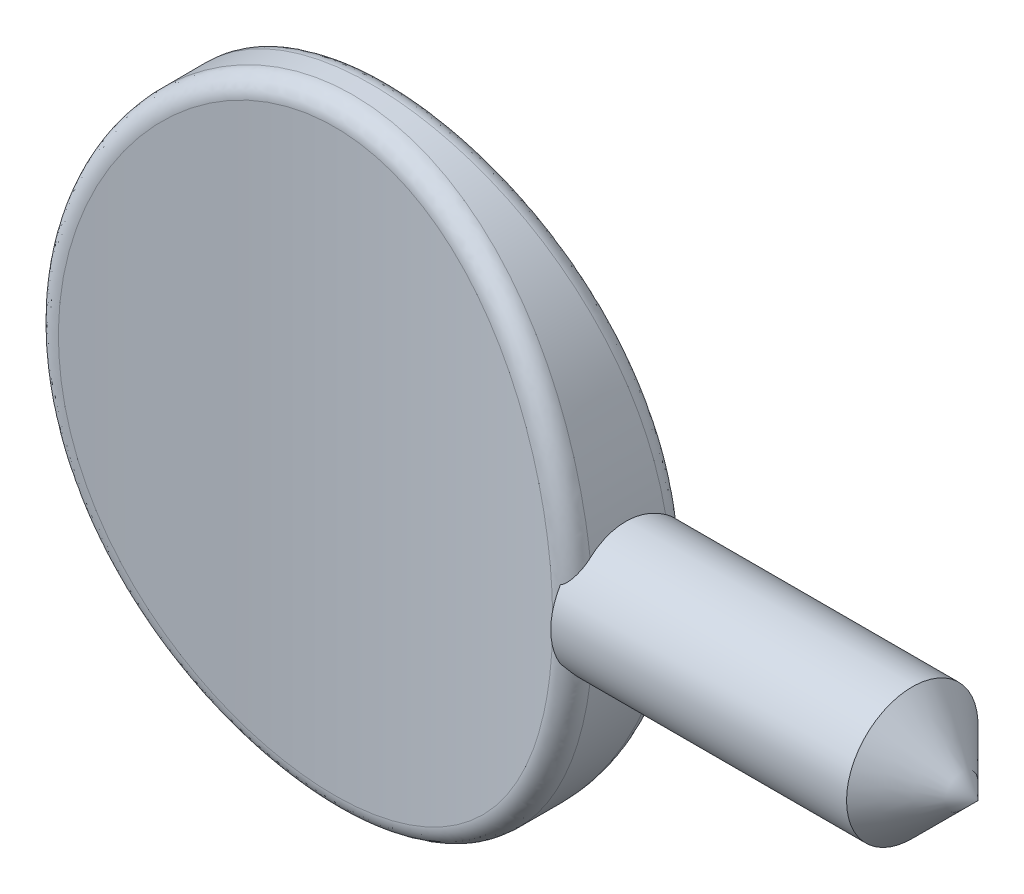
SolidWorks part; units mm, degrees
ref_plane "Front" through (0, 0, 0) normal (0, 0, 1) x (1, 0, 0)
ref_plane "Top" through (0, 0, 0) normal (0, 1, 0) x (1, 0, 0)
ref_plane "Right" through (0, 0, 0) normal (1, 0, 0) x (0, 0, -1)
ref_axis "Axis1" through (-50, 0, 0) along (1, 0, 0)
sketch "Sketch1" plane through (0, 0, 0) normal (0, 0, 1) x (1, 0, 0)
  line L0 (0, 0) -> (22.606, 0) construction
  line L1 (13.208, -2.413) -> (13.208, 2.413)
  line L2 (13.208, -2.413) -> (9.6776, -2.413) construction
  ellipse E0 centre (0, 0) end of major axis (0, -11.303) minor radius 9.906
  dimension "D2" = 3.302
  dimension "B" = 19.812
  dimension "L" = 12.7
extrude "Extrude1" add sketch "Sketch1" along normal mid plane 4.572
sketch "Sketch2" plane through (0, 0, 0) normal (0, 1, 0) x (1, 0, 0)
  line L0 (9.906, 2.286) -> (-9.906, 2.286) construction
  line L1 (0, 0) -> (0, 1.1721) construction
  line L2 (-1.7991, 0) -> (2.0444, 0) construction
  line L3 (-9.906, -2.286) -> (9.906, -2.286) construction
  line L6 (-9.906, 2.286) -> (-9.906, -2.286)
  line L7 (9.906, 2.286) -> (9.906, -2.286)
  arc A0 (-9.906, 2.286) -> (9.906, 2.286) centre (0, 40.2844) ccw
  arc A1 (-9.906, -2.286) -> (9.906, -2.286) centre (0, -40.2844) cw
extrude "Cut-Extrude1" cut sketch "Sketch2" against normal through all and the other way through all flip side to cut
fillet "Fillet3" radius 0.6773 2 edges at (-9.9037, -0.2444, 2.2854) (0.1692, 11.3014, -1.0164)
sketch "Sketch3" plane through (0, 0, 0) normal (0, 1, 0) x (1, 0, 0)
  line L0 (20.193, 2.413) -> (22.606, 0)
  line L1 (0, 0) -> (21.0288, 0) construction
  line L2 (0, 0) -> (22.606, 0) construction
  line L3 (13.208, 2.413) -> (13.208, 0) construction
  line L4 (13.208, 2.413) -> (20.193, 2.413)
  line L6 (13.208, 2.413) -> (9.3367, 2.413)
  line L7 (9.0722, 2.0783) -> (9.0722, 0)
  line L8 (9.3367, 0) -> (9.3367, 2.413) construction
  line L9 (9.0722, 0) -> (22.606, 0)
  arc A0 (9.3367, 2.413) -> (9.0722, 2.0783) centre (8.9927, 2.413) cw
  arc A3 (-9.906, 2.286) -> (9.906, 2.286) centre (0, 40.2844) ccw construction
  dimension "D1" = 45
revolve "Revolve1" add sketch "Sketch3" angle 360 about L0
cosmetic thread "Cosmetic Thread1" [suppressed]
sketch "Sketch4" plane through (0, 0, 0) normal (0, 0, 1) x (1, 0, 0)
  line L0 (0, 0) -> (27.7993, 0) construction
  line L1 (20.0097, 2.413) -> (20.193, 2.0955)
  line L2 (20.193, 2.0955) -> (20.3763, 2.413)
  line L3 (20.3763, 2.413) -> (20.3763, 2.7796)
  line L4 (20.3763, 2.7796) -> (20.0097, 2.7796)
  line L5 (20.0097, 2.7796) -> (20.0097, 2.413)
  line L6 (20.193, 2.413) -> (20.193, -2.413) construction
  dimension "D1" = 4.191
  dimension "D2" = 4.826
revolve "Cut-Revolve10" [suppressed] cut sketch "Sketch4" angle 360 about L0
pattern_linear "LPattern10" [suppressed] count 20 along (-1, 0, 0) of bodies 109
equation "\"D2@Sketch1\" = \"B@Sketch1\" / 6"
equation "\"D1@Fillet3\" = \"C1@Sketch2\" / 3"
equation "\"DIA@Sketch3\" = \"D@Sketch1\""
equation "\"D1@Cosmetic Thread1\" = \"L@Sketch1\" - \"D@Sketch1\" / 2"
equation "\"D1@Sketch4\" = \"D2@Cosmetic Thread1\""
equation "\"D2@Sketch4\" = \"DIA@Sketch3\""
equation "\"D1@LPattern10\" = \"D1@Cosmetic Thread1\" / \"P@LPattern10\" "
